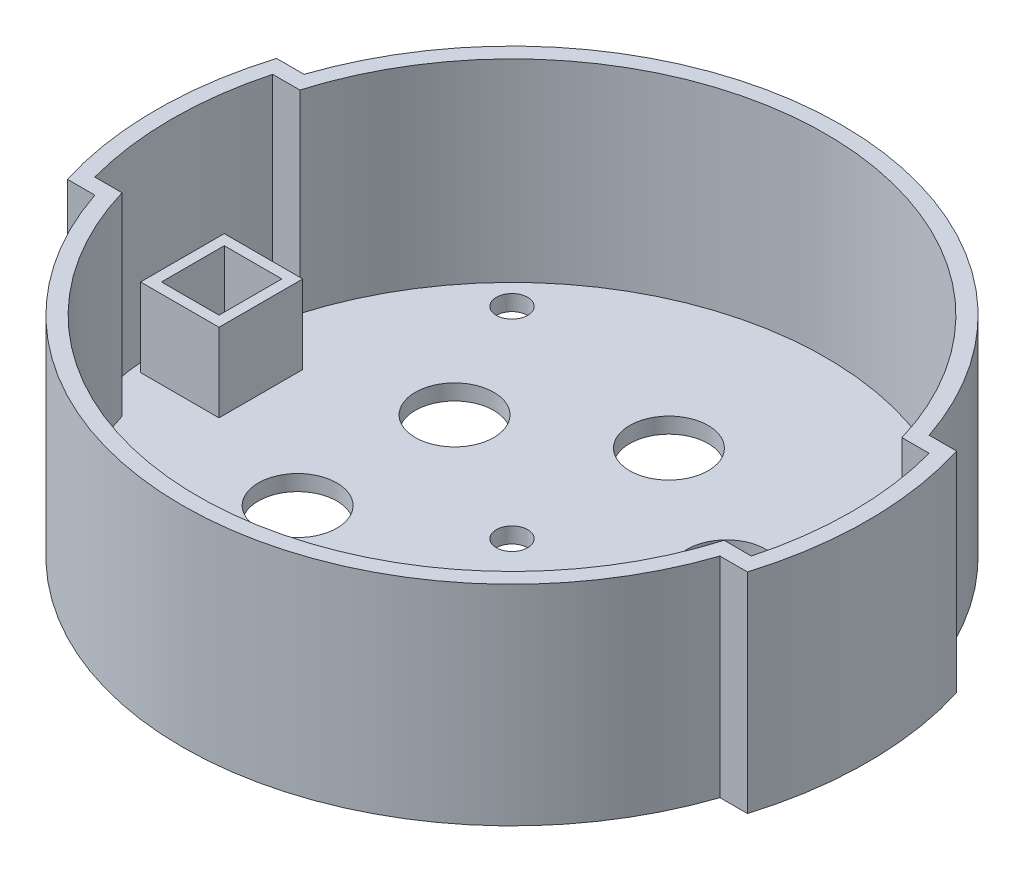
SolidWorks part; units mm, degrees
ref_plane "Front Plane" through (0, 0, 0) normal (0, 0, 1) x (1, 0, 0)
ref_plane "Top Plane" through (0, 0, 0) normal (0, 1, 0) x (1, 0, 0)
ref_plane "Right Plane" through (0, 0, 0) normal (1, 0, 0) x (0, 0, -1)
sketch "Sketch1" plane through (0, 0, 0) normal (0, 1, 0) x (1, 0, 0)
  circle A0 centre (0, 0) radius 68
  dimension "D1" = 136
extrude "Boss-Extrude1" add sketch "Sketch1" along normal blind 40
sketch "Sketch2" plane through (0, 40, 0) normal (0, 1, 0) x (1, 0, 0)
  line L1 (0, 37.0764) -> (0, -27.4787) construction
  line L5 (-59.7411, -20) -> (-64.9923, -20)
  line L6 (-59.7411, 20) -> (-64.9923, 20)
  line L7 (59.7411, -20) -> (64.9923, -20)
  line L8 (59.7411, 20) -> (64.9923, 20)
  line L9 (-28.4675, 0) -> (19.3594, 0) construction
  arc A0 (-59.7411, -20) -> (59.7411, -20) centre (0, 0) ccw
  arc A1 (-64.9923, -20) -> (64.9923, -20) centre (0, 0) ccw
  circle A2 centre (0, 0) radius 68 construction
  arc A3 (59.7411, 20) -> (-59.7411, 20) centre (0, 0) ccw
  arc A4 (64.9923, 20) -> (-64.9923, 20) centre (0, 0) ccw
  dimension "D1" = 126
  dimension "D2" = 40
  dimension "D3" = 40
extrude "Cut-Extrude1" cut sketch "Sketch2" against normal up to surface (40 mm away) up to face at (0, 0, 68)
shell "Shell1" thickness 3 removed face at (0, 40, 0)
sketch "Sketch3" plane through (0, 0, 0) normal (0, -1, 0) x (1, 0, 0)
  line L0 (-78.2757, 0) -> (93.912, 0) construction
  line L1 (0, -51.8142) -> (0, 50.9292) construction
  line L2 (-7.0646, -7.0646) -> (9.5136, 9.5136) construction
  circle A0 centre (-38.4666, 38.4666) radius 3
  circle A1 centre (38.4666, -38.4666) radius 3
  circle A2 centre (0, 30) radius 7.5
  circle A3 centre (25.9808, 15) radius 7.5
  circle A4 centre (25.9808, -15) radius 7.5
  circle A5 centre (0, -30) radius 7.5
  circle A6 centre (-25.9808, -15) radius 7.5
  circle A7 centre (-25.9808, 15) radius 7.5
  circle A8 centre (-38.4666, -38.4666) radius 3
  circle A9 centre (38.4666, 38.4666) radius 3
  point P24 (0, 0)
  dimension "D1" = 6
  dimension "D2" = 6
  dimension "D5" = 15
  dimension "D9" = 6
  dimension "D10" = 6
  dimension "D3" = 54.4
  dimension "D4" = 54.4
  dimension "D6" = 30
  dimension "D8" = 30
  dimension "D11" = 54.4
  dimension "D12" = 54.4
  dimension "D13" = 45
  dimension "D7" = 6
extrude "Cut-Extrude2" cut sketch "Sketch3" against normal through all both and the other way through all
sketch "Sketch4" plane through (0, 3, 0) normal (0, 1, 0) x (1, 0, 0)
  circle A0 centre (0, 0) radius 3
  dimension "D1" = 6
extrude "Cut-Extrude3" cut sketch "Sketch4" against normal up to surface (3 mm away) up to face at (-38.4666, 0, -35.4666)
sketch "Sketch6" plane through (0, 3, 0) normal (0, 1, 0) x (1, 0, 0)
  line L0 (0, 0) -> (-13.2822, 0) construction
  line L1 (-61, 6) -> (-50, 6)
  line L2 (-61, 6) -> (-61, -6)
  line L3 (-61, -6) -> (-50, -6)
  line L4 (-50, 6) -> (-50, -6)
  line L6 (-63, -8) -> (-48, -8)
  line L7 (-63, -8) -> (-63, 8)
  line L8 (-63, 8) -> (-48, 8)
  line L9 (-48, -8) -> (-48, 8)
  point P7 (-50, 0)
  dimension "D1" = 11
  dimension "D2" = 12
  dimension "D3" = 50
  dimension "D4" = 2
  dimension "D5" = 2
  dimension "D6" = 2
  dimension "D7" = 2
extrude "Boss-Extrude2" add sketch "Sketch6" along normal blind 15
sketch "Sketch7" plane through (0, 3, 0) normal (0, 1, 0) x (1, 0, 0)
  line L0 (-61, -6) -> (-50, -6) construction
  line L1 (-61, -6) -> (-50, -6)
  line L2 (-61, -6) -> (-61, 6)
  line L3 (-61, 6) -> (-50, 6)
  line L4 (-50, -6) -> (-50, 6)
  line L5 (-63, -8) -> (-48, -8) construction
  point P8 (-55.5, -8)
  point P9 (-55.5, 6)
  dimension "D1" = 11
  dimension "D2" = 12
extrude "Cut-Extrude5" cut sketch "Sketch7" against normal up to surface (3 mm away) up to face at (0, 0, 3)
